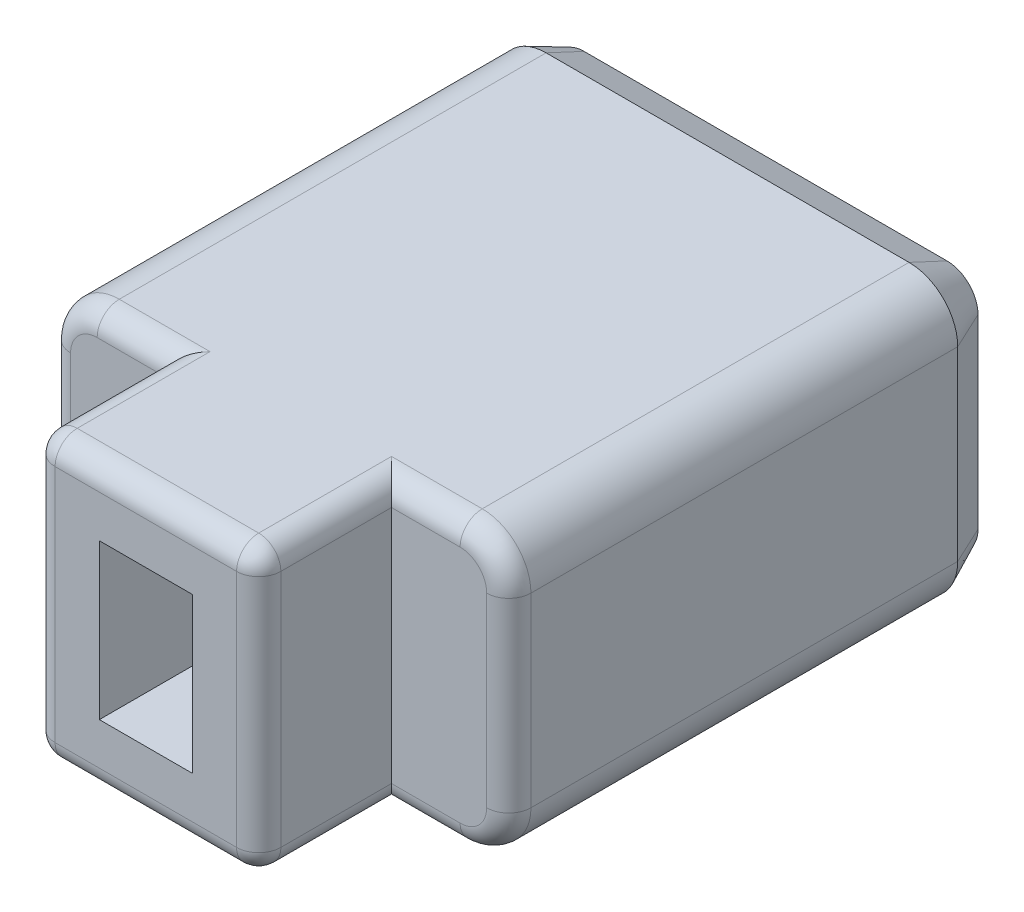
SolidWorks part; units mm, degrees
ref_plane "Plan de face" through (0, 0, 0) normal (0, 0, 1) x (1, 0, 0)
ref_plane "Plan de dessus" through (0, 0, 0) normal (0, 1, 0) x (1, 0, 0)
ref_plane "Plan de droite" through (0, 0, 0) normal (1, 0, 0) x (0, 0, -1)
sketch "Esquisse2" plane through (0, 0, 0) normal (0, 0, 1) x (1, 0, 0)
  line L1 (1.1, 0) -> (9.3, 0)
  line L2 (0, 1.1) -> (0, 5.3)
  line L3 (1.1, 6.4) -> (9.3, 6.4)
  line L4 (10.4, 1.1) -> (10.4, 5.3)
  arc A0 (9.3, 6.4) -> (10.4, 5.3) centre (9.3, 5.3) cw
  arc A1 (9.3, 0) -> (10.4, 1.1) centre (9.3, 1.1) ccw
  arc A2 (1.1, 0) -> (0, 1.1) centre (1.1, 1.1) cw
  arc A3 (0, 5.3) -> (1.1, 6.4) centre (1.1, 5.3) cw
  point P7 (10.4, 6.4)
  point P12 (0, 0)
  point P15 (0, 6.4)
  dimension "D3" = 1.1
  dimension "D1" = 10.4
  dimension "D2" = 6.4
extrude "Boss.-Extru.1" add sketch "Esquisse2" along normal blind 14
sketch "Esquisse3" plane through (0, 0, 14) normal (0, 0, 1) x (1, 0, 0)
  line L0 (0, 5.3) -> (0, 1.1) construction
  line L1 (4.15, 4.95) -> (6.25, 4.95)
  line L2 (4.15, 4.95) -> (4.15, 1.45)
  line L3 (4.15, 1.45) -> (6.25, 1.45)
  line L4 (6.25, 4.95) -> (6.25, 1.45)
  line L5 (10.4, 1.1) -> (10.4, 5.3) construction
  line L6 (9.3, 6.4) -> (1.1, 6.4) construction
  line L7 (1.1, 0) -> (9.3, 0) construction
  dimension "D1" = 2.1
  dimension "D2" = 3.5
  dimension "D3" = 4.15
  dimension "D4" = 4.15
  dimension "D5" = 1.45
  dimension "D6" = 1.45
extrude "Enlèv. mat.-Extru.1" cut sketch "Esquisse3" against normal blind 3
sketch "Esquisse4" plane through (0, 0, 14) normal (0, 0, 1) x (1, 0, 0)
  line L0 (2.65, 6.4) -> (2.65, 0)
  line L1 (9.3, 6.4) -> (1.1, 6.4) construction
  line L2 (1.1, 0) -> (9.3, 0) construction
  line L3 (2.65, 0) -> (7.75, 0)
  line L4 (7.75, 0) -> (7.75, 6.4)
  line L5 (7.75, 6.4) -> (2.65, 6.4)
  line L6 (4.15, 4.95) -> (4.15, 1.45) construction
  line L7 (6.25, 1.45) -> (6.25, 4.95) construction
  dimension "D1" = 1.5
  dimension "D2" = 1.5
extrude "Enlèv. mat.-Extru.2" cut sketch "Esquisse4" against normal blind 3 flip side to cut
fillet "Congé1" radius 0.5 18 edges at (8.525, 0, 11) (10.0778, 0.3222, 11) (10.4, 3.2, 11) (10.0778, 6.0778, 11) (1.875, 6.4, 11) (0.3222, 6.0778, 11) (1.875, 0, 11) (0.3222, 0.3222, 11) (7.75, 6.4, 12.5) (2.65, 6.4, 12.5) (7.75, 0, 12.5) (2.65, 0, 12.5) (2.65, 3.2, 14) (5.2, 6.4, 14) (7.75, 3.2, 14) (5.2, 0, 14) (8.525, 6.4, 11) (0, 3.2, 11)
chamfer "Chanfrein1" distance 0.4 angle 65 8 edges at (5.2, 0, 0) (10.0778, 0.3222, 0) (0.3222, 0.3222, 0) (10.4, 3.2, 0) (0, 3.2, 0) (10.0778, 6.0778, 0) (0.3222, 6.0778, 0) (5.2, 6.4, 0) first distance on face at (5.2, 3.2, 0)
sketch "Esquisse5" plane through (0, 0, 0) normal (0, 0, -1) x (-1, 0, 0)
  line L0 (-0.4, 5.3) -> (-10, 5.3) construction
  arc A0 (-9.3, 6) -> (-10, 5.3) centre (-9.3, 5.3) ccw construction
  text T0 "1" font "Century Gothic" height 4
extrude "Enlèv. mat.-Extru.3" cut sketch "Esquisse5" against normal blind 0.3
extrude "Boss.-Extru.2" add sketch "Esquisse5<2>" along normal blind 0.3 separate body
sketch "Esquisse5<2>" plane through (0, 0, 0) normal (0, 0, -1) x (-1, 0, 0) same geometry as "Esquisse5"
